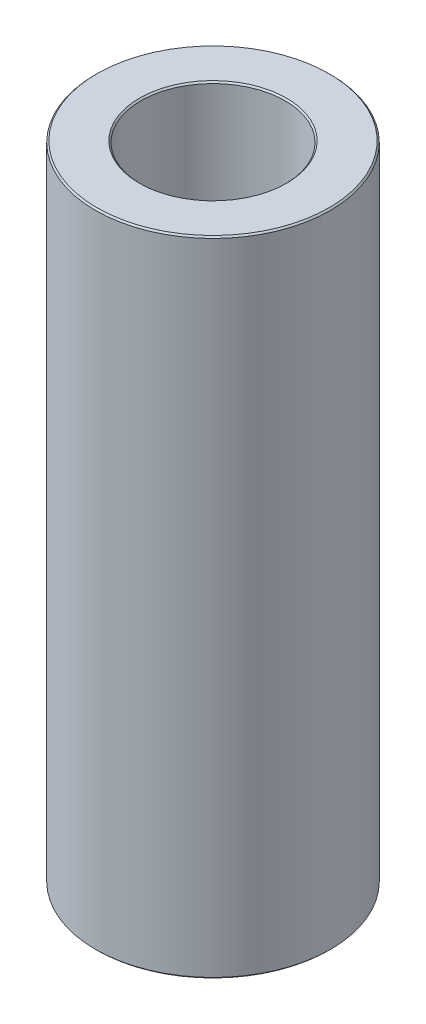
SolidWorks part; units mm, degrees
ref_plane "Front Plane" through (0, 0, 0) normal (0, 0, 1) x (1, 0, 0)
ref_plane "Top Plane" through (0, 0, 0) normal (0, 1, 0) x (1, 0, 0)
ref_plane "Right Plane" through (0, 0, 0) normal (1, 0, 0) x (0, 0, -1)
sketch "Sketch1" plane through (0, 0, 0) normal (0, 1, 0) x (1, 0, 0)
  circle A0 centre (0, 0) radius 32.5
  dimension "SLEEVE_OD" = 65
extrude "Boss-Extrude1" add sketch "Sketch1" along normal blind 177.7243
sketch "Sketch2" plane through (0, 0, 0) normal (0, 1, 0) x (1, 0, 0)
  circle A0 centre (0, 0) radius 19.9506
  dimension "BORE_D" = 39.9013
extrude "Cut-Extrude1" cut sketch "Sketch2" along normal through all
chamfer "Chamfer1" distance 0.4144 angle 45 4 edges at (0, 177.7243, 19.9506) (0, 0, 19.9506) (0, 0, 32.5) (0, 177.7243, 32.5)
